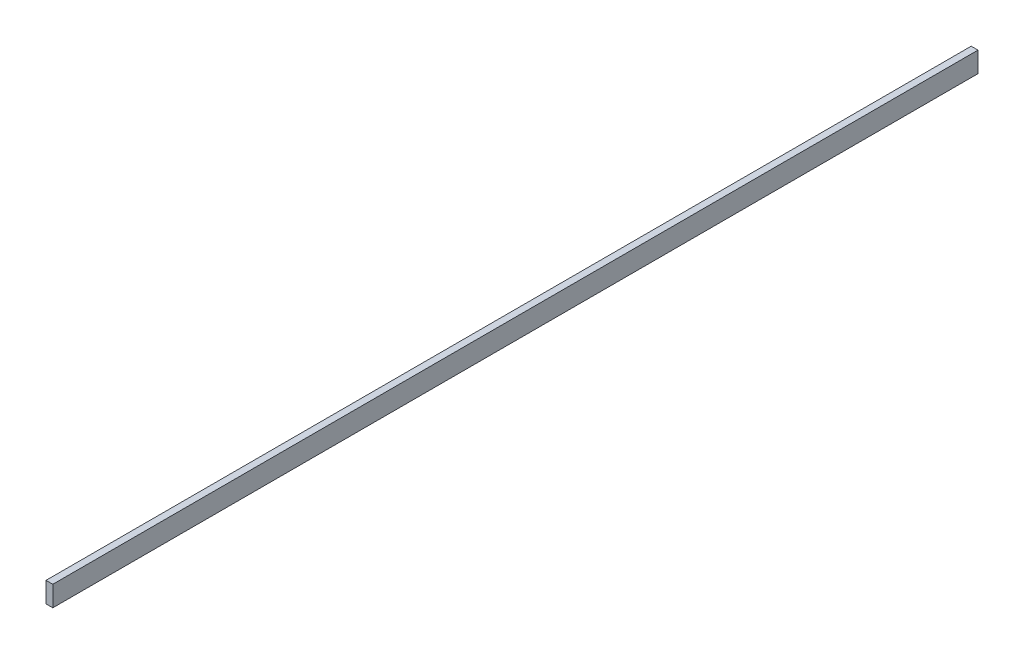
SolidWorks part; units mm, degrees
ref_plane "Ebene vorne" through (0, 0, 0) normal (0, 0, 1) x (1, 0, 0)
ref_plane "Ebene oben" through (0, 0, 0) normal (0, 1, 0) x (1, 0, 0)
ref_plane "Ebene rechts" through (0, 0, 0) normal (1, 0, 0) x (0, 0, -1)
sketch "Skizze1" plane through (0, 0, 0) normal (0, 0, 1) x (1, 0, 0)
  line L1 (0, 0) -> (5, 0)
  line L2 (0, 0) -> (0, 15)
  line L3 (0, 15) -> (5, 15)
  line L4 (5, 0) -> (5, 15)
  dimension "D1" = 5
  dimension "D2" = 15
extrude "Aufsatz-Linear austragen1" add sketch "Skizze1" along normal blind 680
